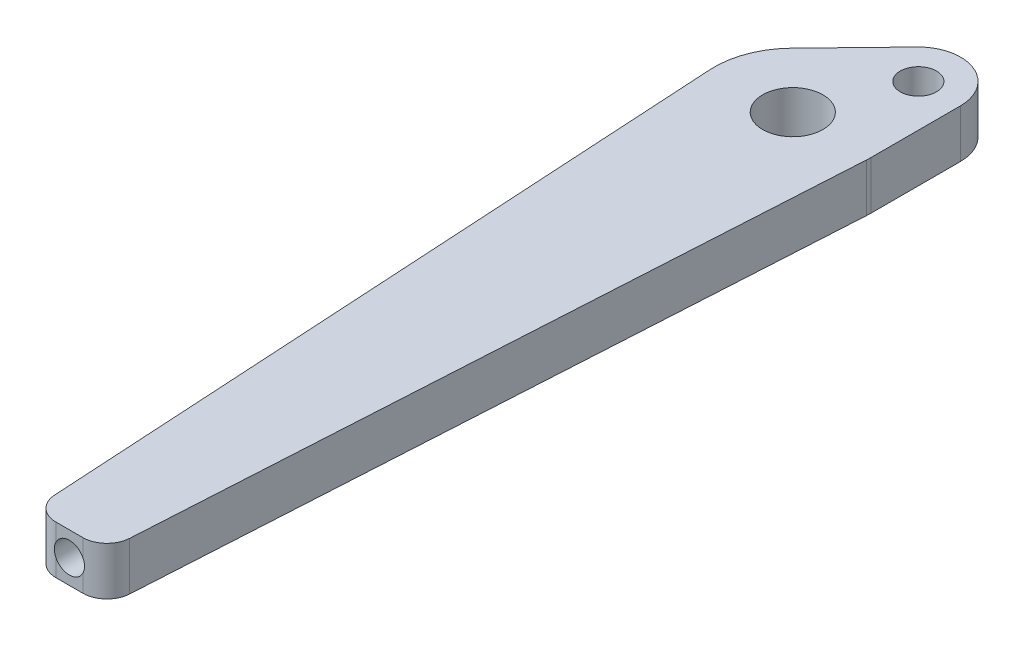
SolidWorks part; units mm, degrees
ref_plane "Front Plane" through (0, 0, 0) normal (0, 0, 1) x (1, 0, 0)
ref_plane "Top Plane" through (0, 0, 0) normal (0, 1, 0) x (1, 0, 0)
ref_plane "Right Plane" through (0, 0, 0) normal (1, 0, 0) x (0, 0, -1)
sketch "Sketch1" plane through (0, 0, 0) normal (0, 1, 0) x (1, 0, 0)
  line L0 (-5.9333, 5.7394) -> (0.6152, 12.509)
  line L1 (8.255, 9.4186) -> (8.255, 0)
  line L2 (8.2409, -0.4822) -> (3.81, -76.2)
  line L3 (-8.2409, -0.4822) -> (-3.81, -76.2)
  line L4 (-3.81, -76.2) -> (3.81, -76.2)
  line L5 (0, 0) -> (0, -76.2) construction
  circle A0 centre (0, 0) radius 3.175
  circle A1 centre (3.81, 9.4186) radius 1.905
  arc A2 (-5.9333, 5.7394) -> (-8.2409, -0.4822) centre (0, 0) ccw
  arc A3 (8.255, 9.4186) -> (0.6152, 12.509) centre (3.81, 9.4186) ccw
  arc A5 (8.2409, -0.4822) -> (8.255, 0) centre (0, 0) ccw
  dimension "D1" = 6.35
  dimension "D2" = 3.81
  dimension "D3" = 76.2
  dimension "D5" = 2.54
  dimension "D6" = 5.08
  dimension "D4" = 7.62
extrude "Boss-Extrude1" add sketch "Sketch1" along normal blind 5.08
sketch "Sketch5" plane through (0, 0, 76.2) normal (0, 0, 1) x (1, 0, 0)
  line L0 (-3.81, 2.54) -> (3.81, 2.54) construction
  line L1 (-3.81, 5.08) -> (-3.81, 0) construction
  line L2 (3.81, 5.08) -> (3.81, 0) construction
  line L3 (0, 5.08) -> (0, 0) construction
  line L4 (-3.81, 5.08) -> (3.81, 5.08) construction
  point P13 (0, 2.54)
hole_wizard "1/8 (0.125) Diameter Hole1" positions "Sketch5" profile "Sketch6" hole size "1/8" standard "ANSI Inch"
sketch "Sketch6" plane through (0, 2.54, 76.2) normal (1, 0, 0) x (0, -1, 0)
  line L0 (0, 0) -> (0, 13.6539)
  line L1 (0, 13.6539) -> (1.5875, 12.7)
  line L2 (1.5875, 12.7) -> (1.5875, 0)
  line L5 (1.5875, 0) -> (0, 0)
  line L10 (0, 13.6539) -> (-1.5875, 12.7) construction
  line L11 (0, -6.35) -> (0, 107.95) construction
  dimension "Hole Dia." = 3.175
  dimension "Hole Depth" = 12.7
  dimension "Drill Angle" = 118
fillet "Fillet1" radius 2.54 2 edges at (-3.81, 2.54, 76.2) (3.81, 2.54, 76.2)
ref_point "Point1"
